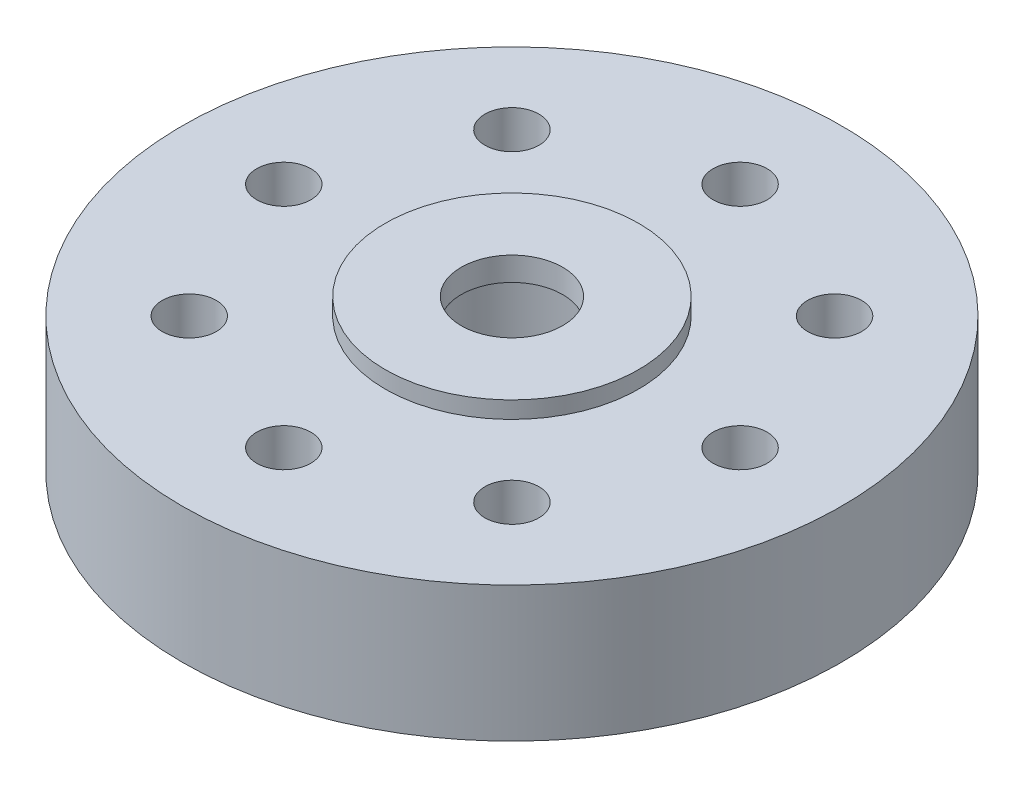
SolidWorks part; units mm, degrees
ref_plane "Alzado" through (0, 0, 0) normal (0, 0, 1) x (1, 0, 0)
ref_plane "Planta" through (0, 0, 0) normal (0, 1, 0) x (1, 0, 0)
ref_plane "Vista lateral" through (0, 0, 0) normal (1, 0, 0) x (0, 0, -1)
sketch "Croquis1" plane through (0, 0, 0) normal (0, 1, 0) x (1, 0, 0)
  line L0 (0, 0) -> (0, 9.75) construction
  line L1 (0, 9.75) -> (0, -9.75) construction
  line L2 (9.75, 0) -> (-9.75, 0) construction
  circle A0 centre (0, 0) radius 9.75
  circle A1 centre (0, 0) radius 1.5
  circle A2 centre (6.75, 0) radius 0.8
  circle A6 centre (0, -6.75) radius 0.8
  circle A7 centre (-6.75, 0) radius 0.8
  circle A8 centre (0, 6.75) radius 0.8
  circle A9 centre (0, 0) radius 3.75
  circle A10 centre (4.773, -4.773) radius 0.8
  circle A11 centre (0, -6.75) radius 0.8
  circle A12 centre (-4.773, -4.773) radius 0.8
  circle A13 centre (-6.75, 0) radius 0.8
  circle A14 centre (-4.773, 4.773) radius 0.8
  circle A15 centre (0, 6.75) radius 0.8
  circle A16 centre (4.773, 4.773) radius 0.8
  point P19 (0, 0)
  point P34 (0, 0)
  dimension "D1" = 19.5
  dimension "D2" = 3
  dimension "D3" = 6.75
  dimension "D4" = 1.6
  dimension "D5" = 4
  dimension "D6" = 7.5
extrude "Saliente-Extruir1" add sketch "Croquis1" along normal mid plane 4 contours A0 A9 A8 A7 A6 A2 | A9 A1 region at (-9.4742, 0, 0) region at (-3.6439, 0, 0)
extrude "Saliente-Extruir2" add sketch "Croquis1<3>" along normal mid plane 5 contours A9 A1 region at (-3.6439, 0, 0)
sketch "Croquis1<3>" plane through (0, 0, 0) normal (0, 1, 0) x (1, 0, 0) same geometry as "Croquis1"
sketch "Croquis2" plane through (0, -2, 0) normal (0, -1, 0) x (1, 0, 0)
  circle A2 centre (0, 0) radius 8.55
  circle A3 centre (0, 0) radius 8.55
  circle A4 centre (6.75, 0) radius 2
  circle A5 centre (4.773, -4.773) radius 2
  circle A6 centre (0, -6.75) radius 2
  circle A7 centre (-4.773, -4.773) radius 2
  circle A8 centre (-6.75, 0) radius 2
  circle A9 centre (-4.773, 4.773) radius 2
  circle A10 centre (0, 6.75) radius 2
  circle A11 centre (4.773, 4.773) radius 2
  circle A12 centre (0, 0) radius 4.4
  circle A14 centre (0, 0) radius 2.5
  point P24 (0, 0)
  circle M2 centre (0, 0) radius 3.75
  dimension "D2" = 8
  dimension "D3" = 4
  dimension "D4" = 8.8
  dimension "D6" = 5
  dimension "D1" = 1.2
extrude "Cortar-Extruir3" cut sketch "Croquis2" against normal blind 3.8 contours A3 A12 A11 A10 A9 A8 A7 A6 A5 A4 region at (4.5098, -2, 0)
extrude "Saliente-Extruir3" add sketch "Croquis2<6>" along normal blind 0.5 contours A12 M2 region at (-4.2755, -2, 0)
sketch "Croquis2<6>" plane through (0, -2, 0) normal (0, -1, 0) x (1, 0, 0) same geometry as "Croquis2"
extrude "Cortar-Extruir4" cut sketch "Croquis2<9>" against normal mid plane 7.6 contours A14 region at (0, -2, 0)
sketch "Croquis2<9>" plane through (0, -2, 0) normal (0, -1, 0) x (1, 0, 0) same geometry as "Croquis2"
